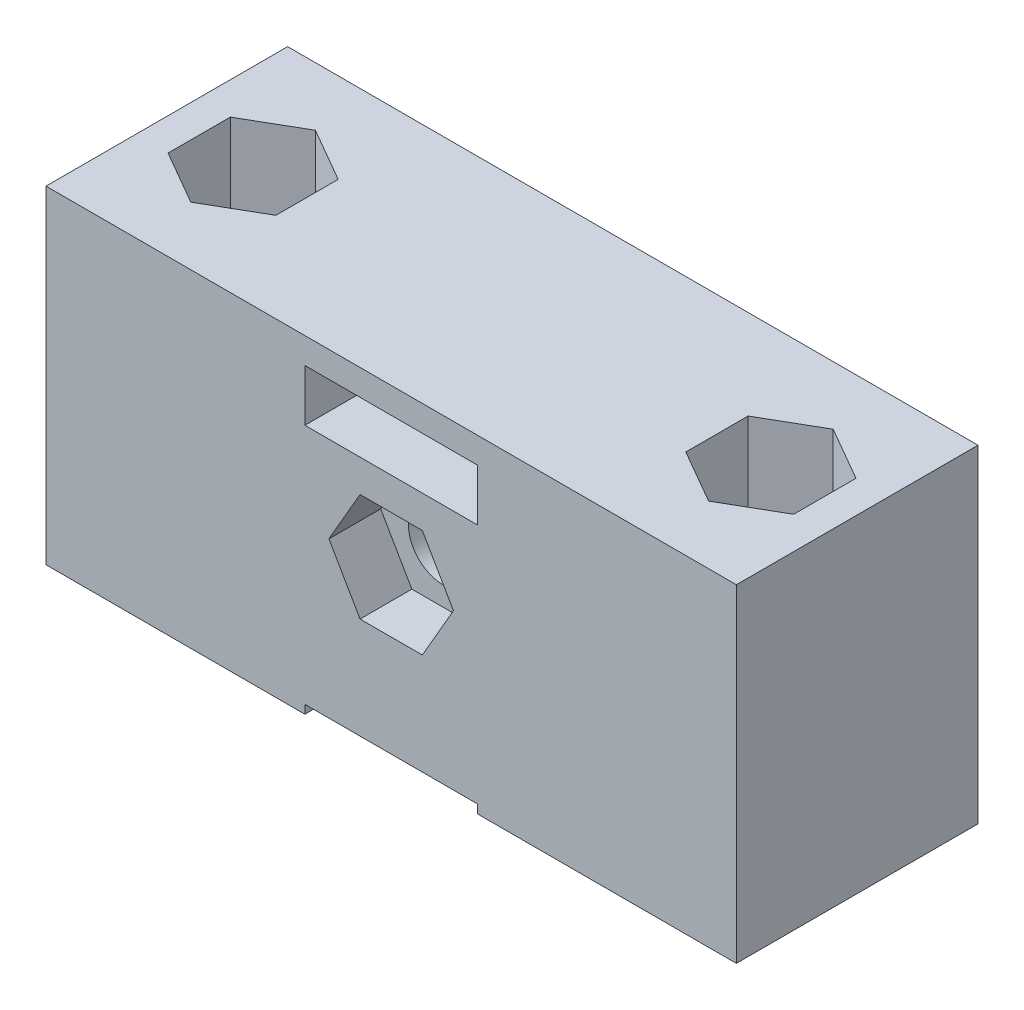
SolidWorks part; units mm, degrees
ref_plane "Front Plane" through (0, 0, 0) normal (0, 0, 1) x (1, 0, 0)
ref_plane "Top Plane" through (0, 0, 0) normal (0, 1, 0) x (1, 0, 0)
ref_plane "Right Plane" through (0, 0, 0) normal (1, 0, 0) x (0, 0, -1)
sketch "Sketch1" plane through (0, 0, 0) normal (0, 1, 0) x (1, 0, 0)
  line L1 (-20, 7) -> (20, 7)
  line L2 (-20, 7) -> (-20, -7)
  line L3 (-20, -7) -> (20, -7)
  line L4 (20, 7) -> (20, -7)
  line L5 (-20, 7) -> (20, -7) construction
  line L6 (-20, -7) -> (20, 7) construction
  point P0 (0, 0)
  dimension "D1" = 40
  dimension "D2" = 14
extrude "Boss-Extrude1" add sketch "Sketch1" along normal blind 19
sketch "Sketch2" plane through (0, 0, 7) normal (0, 0, 1) x (1, 0, 0)
  line L0 (0, 19) -> (0, 0) construction
  line L1 (-20, 19) -> (20, 19) construction
  line L3 (-5, 14.5) -> (5, 14.5)
  line L4 (-5, 14.5) -> (-5, 17.5)
  line L5 (-5, 17.5) -> (5, 17.5)
  line L6 (5, 14.5) -> (5, 17.5)
  line L7 (-5, 14.5) -> (5, 17.5) construction
  line L8 (-5, 17.5) -> (5, 14.5) construction
  line L9 (-5, -0.5) -> (5, -0.5)
  line L10 (-5, -0.5) -> (-5, 0.5)
  line L11 (-5, 0.5) -> (5, 0.5)
  line L12 (5, -0.5) -> (5, 0.5)
  line L13 (-5, -0.5) -> (5, 0.5) construction
  line L14 (-5, 0.5) -> (5, -0.5) construction
  point P5 (0, 16)
  dimension "D1" = 10
  dimension "D2" = 3
  dimension "D3" = 16
  dimension "D4" = 10
  dimension "D5" = 1
extrude "Cut-Extrude1" cut sketch "Sketch2" against normal blind 30
sketch "Sketch3" plane through (0, 0, 7) normal (0, 0, 1) x (1, 0, 0)
  line L0 (0, 19) -> (0, 0) construction
  line L1 (-20, 19) -> (20, 19) construction
  circle A0 centre (0, 9.5) radius 2
  dimension "D1" = 4
extrude "Cut-Extrude2" cut sketch "Sketch3" against normal through all
sketch "Sketch4" plane through (0, 19, 0) normal (0, 1, 0) x (1, 0, 0)
  line L0 (-20, 0) -> (20, 0) construction
  line L1 (-20, 7) -> (-20, -7) construction
  line L2 (20, -7) -> (20, 7) construction
  line L3 (0, 7) -> (0, -7) construction
  line L4 (20, 7) -> (-20, 7) construction
  line L5 (-20, -7) -> (20, -7) construction
  circle A0 centre (-15, 0) radius 1.6
  circle A1 centre (15, 0) radius 1.6
  dimension "D1" = 3.2
  dimension "D2" = 15
extrude "Cut-Extrude3" cut sketch "Sketch4" against normal through all
sketch "Sketch8" plane through (0, 0, 0) normal (0, -1, 0) x (-1, 0, 0)
  line L0 (-5, 7) -> (-5, -7) construction
  line L1 (5, -7) -> (-5, -7)
  line L2 (5, -7) -> (5, -6)
  line L3 (5, -6) -> (-5, -6)
  line L4 (-5, -7) -> (-5, -6)
  dimension "D1" = 1
extrude "Boss-Extrude2" [suppressed] add sketch "Sketch8" against normal up to next
sketch "Sketch9" plane through (0, 19, 0) normal (0, 1, 0) x (1, 0, 0)
  line L0 (0, 7) -> (0, -7) construction
  line L1 (-15, 3.6084) -> (-18.125, 1.8042)
  line L2 (-18.125, 1.8042) -> (-18.125, -1.8042)
  line L3 (-18.125, -1.8042) -> (-15, -3.6084)
  line L4 (-15, -3.6084) -> (-11.875, -1.8042)
  line L5 (-11.875, -1.8042) -> (-11.875, 1.8042)
  line L6 (-11.875, 1.8042) -> (-15, 3.6084)
  line L7 (20, 7) -> (-20, 7) construction
  line L8 (-20, -7) -> (20, -7) construction
  line L9 (11.875, 1.8042) -> (15, 3.6084)
  line L10 (11.875, -1.8042) -> (11.875, 1.8042)
  line L11 (15, -3.6084) -> (11.875, -1.8042)
  line L12 (18.125, -1.8042) -> (15, -3.6084)
  line L13 (18.125, 1.8042) -> (18.125, -1.8042)
  line L14 (15, 3.6084) -> (18.125, 1.8042)
  circle A0 centre (-15, 0) radius 3.125 construction
  circle A1 centre (15, 0) radius 3.125 construction
  dimension "D1" = 6.25
extrude "Cut-Extrude4" cut sketch "Sketch9" against normal blind 10
sketch "Sketch10" plane through (0, 0, 7) normal (0, 0, 1) x (1, 0, 0)
  line L1 (1.8042, 12.625) -> (-1.8042, 12.625)
  line L2 (-1.8042, 12.625) -> (-3.6084, 9.5)
  line L3 (-3.6084, 9.5) -> (-1.8042, 6.375)
  line L4 (-1.8042, 6.375) -> (1.8042, 6.375)
  line L5 (1.8042, 6.375) -> (3.6084, 9.5)
  line L6 (3.6084, 9.5) -> (1.8042, 12.625)
  circle A0 centre (0, 9.5) radius 3.125 construction
  dimension "D1" = 6.25
extrude "Cut-Extrude5" cut sketch "Sketch10" against normal blind 3
equation "\"X-ROD-SPACING\"=45"
equation "\"Y-ROD-SPACING\"=75"
equation "\"Z-ROD-SPACING\"=17.5"
equation "\"Y-BED-OFFSET\"=2"
equation "\"Y-BED-ROD-INSET\"=3.5"
equation "\"Y-BED-SCREW-SPACING\"=209"
equation "\"Y-BED-SCREW-CUTOUT-SLOT-HEIGHT\"=2"
equation "\"T-SLOT-NUT-FILLET-RADIUS\"=0.5"
equation "\"T-SLOT-SCREW-SHAFT-RADIUS\"=1.55"
equation "\"T-SLOT-SCREW-SHAFT-CUTOUT-LENGTH\"=11.0"
equation "\"T-SLOT-NUT-DEPTH\"=3.5"
equation "\"T-SLOT-NUT-WIDTH\"=2.85"
equation "\"T-SLOT-NUT-END-DISTANCE\"=8"
equation "\"ACRYLIC-THICKNESS\"=10"
equation "\"ACRYLIC-THICKNESS2\"=4.5"
equation "\"ACRYLIC-TAB-CUTOUT-SIZE\"=\"ACRYLIC-THICKNESS\"+\"ACRYLIC-TAB-TOLERANCE\"*2"
equation "\"ACRYLIC-TAB-TOLERANCE\"=-.05"
equation "\"ACRYLIC-TAB-WIDTH\"=\"ACRYLIC-THICKNESS\""
equation "\"ACRYLIC-M3-HOLE\"=2.9"
equation "\"SMOOTHROD-CAP-SCREW-DISTANCE\"=20"
equation "\"FRAME-WIDTH-INNER\"=370"
equation "\"NEMA17-HOLE-SPACING\"=31"
equation "\"NEMA17-CENTRAL-CUTOUT\"=22.5"
equation "\"Z-BRACKET-REACH\"=55"
equation "\"Z-ROD-INSET\"=16"
equation "\"TOP-BRACKET-SPACING\"=40"
equation "\"SMOOTHROD-X-LENGTH\"=350"
equation "\"SMOOTHROD-Y-LENGTH\"=350"
equation "\"SMOOTHROD-Z-LENGTH\"=350"
equation "\"SMOOTHROD-TIGHTENING-HEADROOM\"=.25"
equation "\"LEADSCREW-Z-LENGTH\"=300"
equation "\"SCREW-LENGTH-FRAME\"=\"ACRYLIC-THICKNESS\" + 10"
equation "\"SCREW-LENGTH-MOTOR\"=\"ACRYLIC-THICKNESS\" + 5"
equation "\"SCREW-LENGTH-EXTRUDER\"=28"
equation "\"SCREW-HEAD-RADIUS\"=6"
equation "\"PRINTED-M3-HOLE\"=3.5"
equation "\"PRINTED-X-SMOOTHROD-DIAMETER\"=8.4"
equation "\"PRINTED-X-SMOOTHROD-CUTOUT\"=10"
equation "\"PRINTED-X-BASE-HEIGHT\"=10"
equation "\"PRINTED-LM8UU-CUTOUT-SIZE\"=15.5"
equation "\"PRINTED-LM8UU-CUTOUT-LENGTH\"=24.5"
equation "\"PRINTED-X-IDLER-HEIGHT\"=16"
equation "\"PSU-MOUNTING-WIDTH\"=95"
equation "\"PSU-MOUNTING-HEIGHT\"=177"
equation "\"Y-BELT-TO-ROD-DISTANCE\"=20"
equation "\"SPOOL-HOLDER-ROD-SPACING\"=150"
equation "\"ACRYLIC-X-CARRIAGE-WIDTH\"=55"
equation "\"ACRYLIC-X-CARRIAGE-HEIGHT\"=75"
equation "\"ACRYLIC-X-CARRIAGE-LM8UU-CUTOUT-WIDTH\"=24.25"
equation "\"ACRYLIC-X-CARRIAGE-LM8UU-CUTOUT-HEIGHT\"=11.0"
equation "\"ACRYLIC-X-CARRIAGE-SCREW-SPACING-X\"=15"
equation "\"ACRYLIC-X-CARRIAGE-SCREW-SPACING-Y\"=33"
equation "\"ACRYLIC-X-CARRIAGE-CENTER-TAB-SPACING\"=14"
equation "\"ACRYLIC-X-CARRIAGE-EXTRUDER-OFFSET\"=26"
equation "\"ACRYLIC-X-CARRIAGE-EXTRUDER-ANGLE\"=90"
equation "\"ACRYLIC-X-CARRIAGE-EXTRUDER-SHELF-DEPTH\"=\"ACRYLIC-X-CARRIAGE-EXTRUDER-OFFSET\" + 28"
equation "\"ACRYLIC-X-CARRIAGE-EXTRUDER-BRACE-SPACING\"=23"
equation "\"ACRYLIC-X-CARRIAGE-EXTRUDER-BRACE-TAB-OFFSET\"=20"
equation "\"ACRYLIC-X-CARRIAGE-EXTRUDER-BRACE-HEIGHT\"=35"
equation "\"ACRYLIC-X-CARRIAGE-EXTRUDER-BRACE-SCREW-SPACING\"=22"
equation "\"ACRYLIC-X-CARRIAGE-DUAL-WIDTH-MULTIPLIER\"=1.65"
equation "\"ACRYLIC-X-CARRIAGE-DUAL-HOTEND-SPACING\"=42"
equation "\"ACRYLIC-X-CARRIAGE-DUAL-WIDTH\"=75"
equation "\"ACRYLIC-X-CARRIAGE-DUAL-HOTEND-SEPARATION\"=36"
equation "\"ACRYLIC-X-CARRIAGE-DUAL-MOUNT-PLATE-DEPTH\"=75"
equation "\"ACRYLIC-X-CARRIAGE-DUAL-MOUNT-BRACE-WIDTH\"=33"
equation "\"ACRYLIC-X-CARRIAGE-DUAL-MOUNT-SCREW-WIDTH\"=40"
equation "\"BLOWER-FAN-WIDTH\"=15"
equation "\"PRINTED-M3-NUT-AF\"=6.25"
equation "\"D1@Sketch9\"=\"PRINTED-M3-NUT-AF\""
equation "\"D1@Sketch10\"=\"PRINTED-M3-NUT-AF\""
